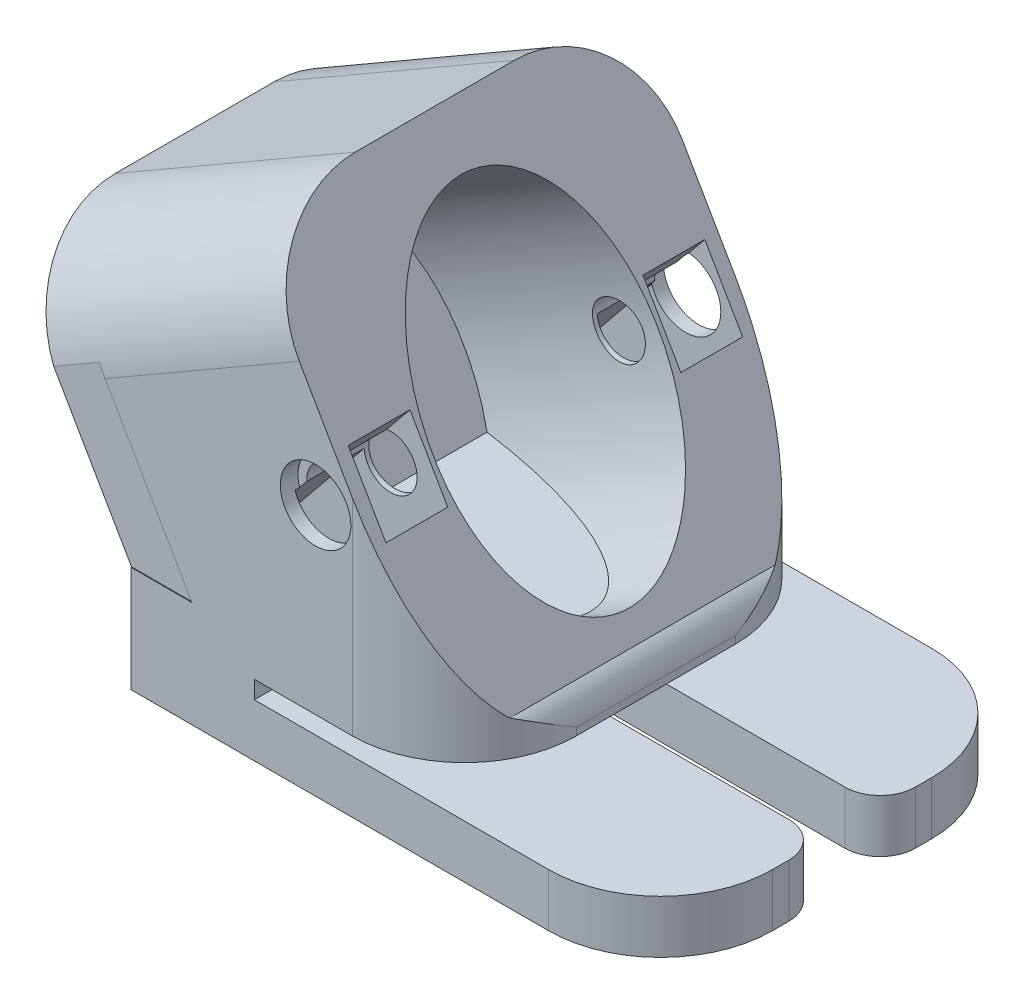
SolidWorks part; units mm, degrees
note: The reader was unsure of these and kept them because the rebuilt part matched: shared geometry of "Sketch7<3>".
ref_plane "Front Plane" through (0, 0, 0) normal (0, 0, 1) x (1, 0, 0)
ref_plane "Top Plane" through (0, 0, 0) normal (0, 1, 0) x (1, 0, 0)
ref_plane "Right Plane" through (0, 0, 0) normal (1, 0, 0) x (0, 0, -1)
sketch "Sketch1" plane through (0, 0, 0) normal (0, 0, 1) x (1, 0, 0)
  line L0 (0, 0) -> (16.4978, 9.525)
  line L1 (0, 0) -> (20.7767, 0) construction
  line L2 (12.7, 0) -> (19.6728, 4.0257)
  line L3 (19.6928, 3.9911) -> (16.4978, 9.525) construction
  point P9 (14.1735, 0.8507)
  dimension "D1" = 19.05
  dimension "D2" = 30
  dimension "D3" = 6.35
  dimension "D4" = 8.0515
  dimension "D5" = 6.35
ref_plane "Plane1" through (16.4978, 9.525, 0) normal (0.866, 0.5, 0) x (0, 0, -1)
sketch "Sketch2" plane through (16.4978, 9.525, 0) normal (0.866, 0.5, 0) x (0, 0, -1)
  line L0 (0, 100000) -> (0, -100010.3884) construction
  line L1 (10.85, 12.525) -> (10.85, -12.525)
  line L2 (10.85, 12.525) -> (-10.85, 12.525)
  line L3 (10.85, -12.525) -> (-10.85, -12.525)
  line L4 (-10.85, 12.525) -> (-10.85, -12.525)
  line L5 (10.85, 12.525) -> (-10.85, -12.525) construction
  line L6 (10.85, -12.525) -> (-10.85, 12.525) construction
  ellipse E0 centre (0, 0) end of major axis (0, 9.525) minor radius 6.35
  point P1 (-10.85, 0)
  point P7 (0, -12.525)
  dimension "D1" = 19.05
  dimension "D2" = 12.7
  dimension "D3" = 4.5
  dimension "D4" = 3
extrude "Boss-Extrude1" add sketch "Sketch2" against normal blind 12.7
sketch "Sketch3" plane through (5.4993, 3.175, 0) normal (-0.866, -0.5, 0) x (0, 0, 1)
  line L0 (-10.85, 12.525) -> (-10.85, -12.525)
  line L1 (-10.85, 12.525) -> (10.8107, 12.525)
  line L2 (-10.85, -12.525) -> (10.8107, -12.525)
  line L3 (10.8107, 12.525) -> (10.8107, -12.525)
extrude "Boss-Extrude2" add sketch "Sketch3" along normal blind 3
sketch "Sketch5" plane through (0, 0, 0) normal (0, 1, 0) x (-1, 0, 0)
  line L0 (-22.7603, 10.85) -> (-22.7603, -10.85)
  line L1 (-22.7603, 10.85) -> (-3.8682, 10.85)
  line L2 (-22.7603, -10.85) -> (-3.8682, -10.85)
  line L3 (-3.8682, 10.85) -> (-3.8682, -10.85)
  line L8 (-22.7603, 10.85) -> (-22.7603, -10.85) construction
extrude "Boss-Extrude3" add sketch "Sketch5" against normal blind 2
sketch "Sketch6" plane through (0, -2, 0) normal (0, -1, 0) x (1, 0, 0)
  line L0 (3.8682, -10.85) -> (3.8682, 10.85)
  line L1 (3.8682, -10.85) -> (33.8682, -10.85)
  line L2 (3.8682, 10.85) -> (33.8682, 10.85)
  line L3 (33.8682, -10.85) -> (33.8682, 10.85)
  line L10 (3.8682, 10.85) -> (8.487, 10.85) construction
  line L11 (3.8682, -10.85) -> (3.8682, 10.85) construction
  dimension "D1" = 30
extrude "Boss-Extrude4" add sketch "Sketch6" along normal blind 4
sketch "Sketch7" plane through (33.8682, 0, 0) normal (1, 0, 0) x (0, 0, -1)
  line L0 (-10.85, -2) -> (10.85, -2)
  line L1 (-10.85, -2) -> (-10.85, -3)
  line L2 (10.85, -2) -> (10.85, -3)
  line L3 (-10.85, -3) -> (10.85, -3)
  line L4 (-1.5875, -3) -> (1.5875, -3)
  line L5 (-10.85, -6) -> (-10.85, -2) construction
  line L6 (-10.85, -6) -> (10.85, -6)
  line L7 (-10.85, -6) -> (-10.85, -13.2725)
  line L8 (10.85, -6) -> (10.85, -13.2725)
  line L9 (-10.85, -13.2725) -> (10.85, -13.2725)
  line L10 (-1.5875, -3) -> (-1.5875, -6)
  line L11 (1.5875, -3) -> (1.5875, -6)
  line L12 (-1.5875, -6) -> (1.5875, -6)
  point P0 (0, -3)
  point P11 (0, -3)
  line M4 (-10.85, -6) -> (10.85, -6)
  dimension "D1" = 1
  dimension "D2" = 3.175
extrude "Cut-Extrude2" cut sketch "Sketch7" against normal blind 23 contours L2 L3 L1 L0 | L10 L12 L11 L4
extrude "Cut-Extrude3" cut sketch "Sketch7<3>" against normal through all contours L7 L9 L8 M4
sketch "Sketch7<3>" plane through (33.8682, 0, 0) normal (1, 0, 0) x (0, 0, -1) same geometry as "Sketch7"
ref_plane "Plane2" through (3.175, -5.4993, 0) normal (0.5, -0.866, 0) x (0.866, 0.5, 0)
sketch "Sketch8" plane through (3.175, -5.4993, 6.35) normal (0.5, -0.866, 0) x (0.75, 0.433, -0.5)
  line L0 (13.7985, 1.5003) -> (14.5485, 0.2012)
  line L1 (13.7985, 1.5003) -> (-3.522, -8.4997)
  line L2 (14.5485, 0.2012) -> (-2.772, -9.7988)
  line L3 (-3.522, -8.4997) -> (-2.772, -9.7988)
  line L4 (12.7, 0) -> (19.6728, 4.0257) construction
  dimension "D1" = 1.5
  dimension "D2" = 20
ref_plane "Plane3" through (19.6728, 0, 0) normal (1, 0, 0) x (0, 0, -1)
sketch "Sketch11" plane through (19.6728, 0.1949, 0) normal (-1, 0, 0) x (0, 0, -1)
  circle A0 centre (0, -3.8309) radius 1
  dimension "D1" = 2
extrude "Cut-Extrude8" cut sketch "Sketch11" along normal through all
sketch "Sketch13" plane through (0, 0, 0) normal (0, 0, 1) x (1, 0, 0)
  line L0 (16.4978, 9.525) -> (3.8682, -6)
ref_plane "Plane4" through (16.4978, 9.525, 0) normal (0.6311, 0.7757, 0) x (0.7757, -0.6311, 0)
sketch "Sketch15" plane through (16.4978, 9.525, 0) normal (0.6311, 0.7757, 0) x (0.7757, -0.6311, 0)
  line L0 (-11.7031, -10.85) -> (10.2768, -10.85) construction
  line L1 (-2, -6.6) -> (2, -6.6)
  line L2 (-2, -6.6) -> (-2, -10.1)
  line L3 (-2, -10.1) -> (2, -10.1)
  line L4 (2, -6.6) -> (2, -10.1)
  line L6 (0, 0) -> (0, -5.6108) construction
  point P8 (0, -10.1)
  dimension "D1" = 3.5
  dimension "D2" = 4
  dimension "D3" = 0.75
extrude "Cut-Extrude9" cut sketch "Sketch15" against normal through all both and the other way through all
sketch "Sketch9" plane through (0, 0, -10.85) normal (0, 0, -1) x (-1, 0, 0)
  line L0 (0, 0) -> (-16.4978, 9.525) construction
  line L1 (-10.2353, 20.372) -> (-21.997, 0) construction
  circle A0 centre (-14.3327, 8.275) radius 1.5
  dimension "D1" = 3
  dimension "D2" = 2.5
extrude "Cut-Extrude4" cut sketch "Sketch9" against normal up to next contours A0
sketch "Sketch10" plane through (0, 0, -10.85) normal (0, 0, -1) x (-1, 0, 0)
  circle A0 centre (-14.3327, 8.275) radius 2
  dimension "D1" = 4
extrude "Cut-Extrude7" cut sketch "Sketch10" against normal blind 1
mirror "Mirror1" about plane through (0, 0, 0) normal (0, 0, 1) of "Cut-Extrude9", "Cut-Extrude4", "Cut-Extrude7"
fillet "Fillet5" radius 6.35 6 edges at (33.8682, -4.5, 10.85) (33.8682, -4.5, -10.85) (22.7603, -1, -10.85) (22.7603, -1, 10.85) (4.736, 17.197, 10.85) (3.437, 16.447, -10.85)
fillet "Fillet6" radius 2 2 edges at (33.8682, -4.5, -1.5875) (33.8682, -4.5, 1.5875)
fillet "Fillet7" radius 2 1 edges at (22.7603, 0, 0)
